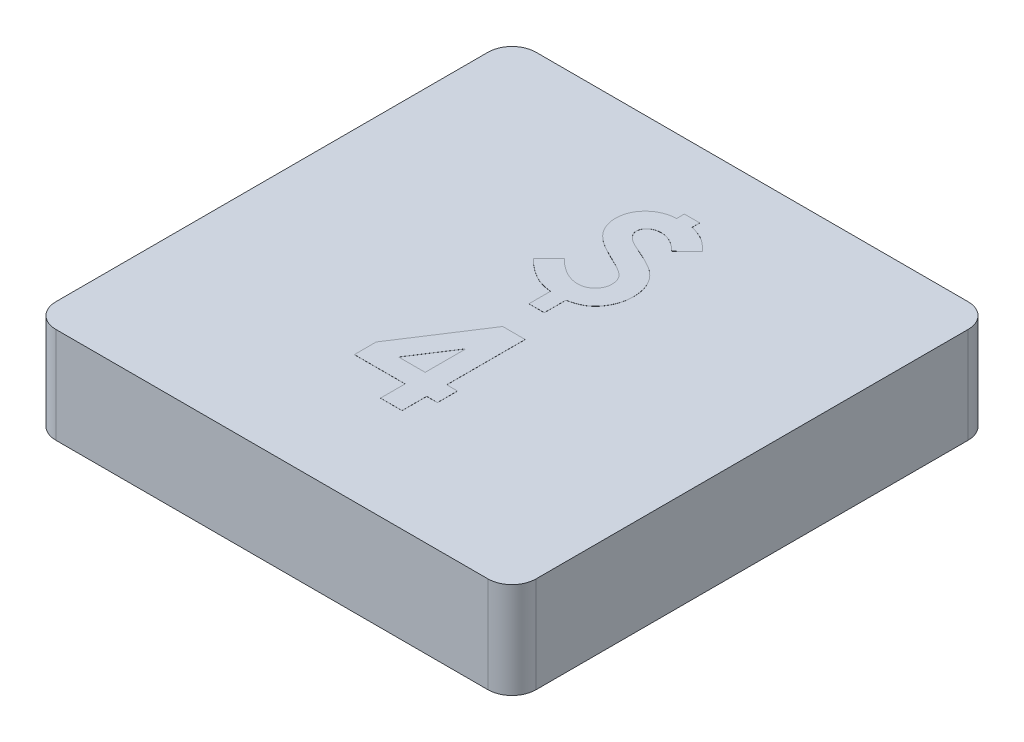
SolidWorks part; units mm, degrees
ref_plane "Front Plane" through (0, 0, 0) normal (0, 0, 1) x (1, 0, 0)
ref_plane "Top Plane" through (0, 0, 0) normal (0, 1, 0) x (1, 0, 0)
ref_plane "Right Plane" through (0, 0, 0) normal (1, 0, 0) x (0, 0, -1)
sketch "Sketch1" plane through (0, 0, 0) normal (0, 1, 0) x (1, 0, 0)
  line L0 (0, 0) -> (12.7, 0)
  line L1 (12.7, 0) -> (12.7, 12.7)
  line L2 (12.7, 12.7) -> (0, 12.7)
  line L3 (0, 12.7) -> (0, 0)
  dimension "D1" = 12.7
  dimension "D2" = 12.7
extrude "Boss-Extrude1" add sketch "Sketch1" along normal blind 2.54
fillet "Fillet1" radius 0.635 4 edges at (0, 1.27, -12.7) (12.7, 1.27, -12.7) (12.7, 1.27, 0) (0, 1.27, 0)
shell "Shell1" thickness 0.635 removed face at (6.35, 0, -6.35)
sketch "Sketch2" plane through (0, 1.905, 0) normal (0, -1, 0) x (-1, 0, 0)
  line L0 (-0.635, 6.35) -> (-12.065, 6.35) construction
  line L1 (-0.635, 12.065) -> (-0.635, 0.635) construction
  line L2 (-12.065, 0.635) -> (-12.065, 12.065) construction
  line L3 (-6.35, 0.635) -> (-6.35, 12.065) construction
  line L4 (-0.635, 0.635) -> (-12.065, 0.635) construction
  line L5 (-12.065, 12.065) -> (-0.635, 12.065) construction
  circle A0 centre (-6.35, 6.35) radius 2.54
  dimension "D1" = 5.08
extrude "Boss-Extrude2" add sketch "Sketch2" along normal up to surface (1.905 mm away) up to face at (6.35, 0, -6.35)
sketch "Sketch4" plane through (0, 2.54, 0) normal (0, 1, 0) x (1, 0, 0)
  line L0 (0, 12.065) -> (0, 0.635) construction
  line L1 (12.065, 12.7) -> (0.635, 12.7) construction
  line L2 (0.635, 0) -> (12.065, 0) construction
  text T0 "<b>4</b>"
  text T1 "<b>$</b>"
  dimension "D1" = 5.207
  dimension "D2" = 5.08
  dimension "D3" = 5.207
  dimension "D4" = 2.7178
extrude "Boss-Extrude4" add sketch "Sketch4" along normal blind 0.0025
